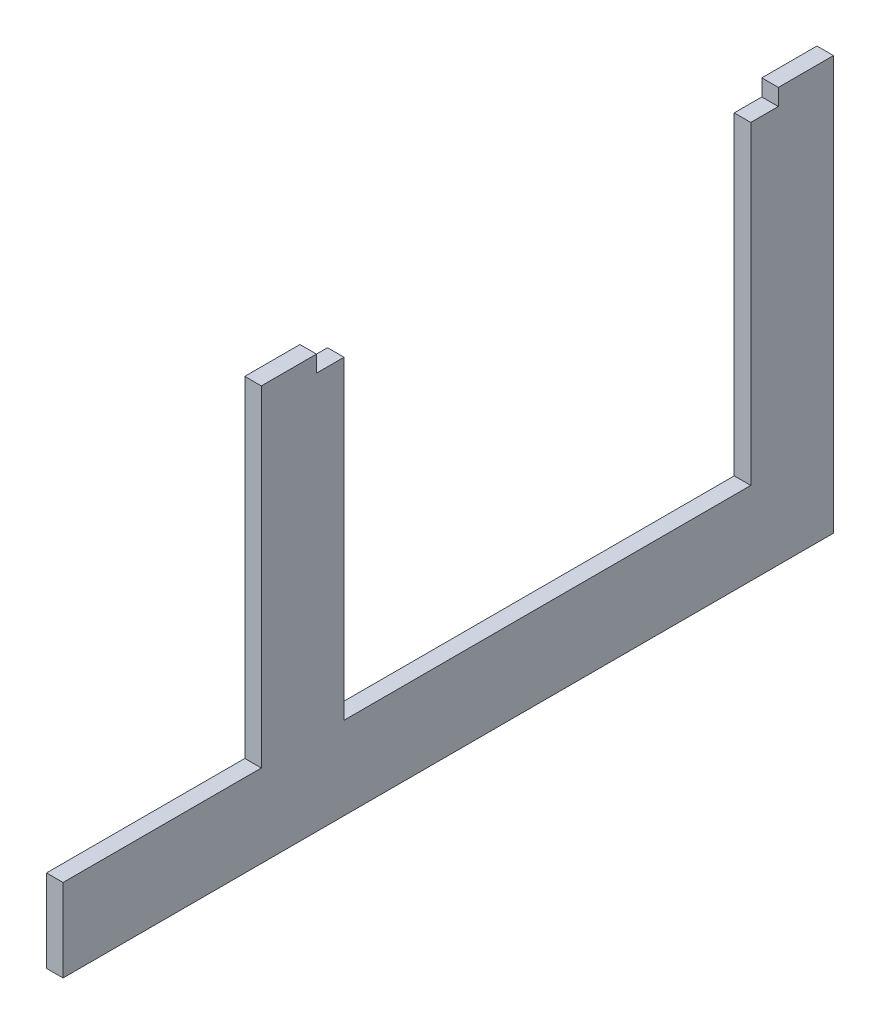
SolidWorks part; units mm, degrees
ref_plane "Front Plane" through (0, 0, 0) normal (0, 0, 1) x (1, 0, 0)
ref_plane "Top Plane" through (0, 0, 0) normal (0, 1, 0) x (1, 0, 0)
ref_plane "Right Plane" through (0, 0, 0) normal (1, 0, 0) x (0, 0, -1)
sketch "Sketch1" plane through (0, 0, 0) normal (0, 1, 0) x (1, 0, 0)
  line L0 (0, 0) -> (0, 103.7444) construction
  line L1 (-36.8722, 0) -> (36.8722, 0) construction
  line L2 (-36.8722, 0) -> (-36.8722, 103.7444)
  line L3 (-36.8722, 103.7444) -> (36.8722, 103.7444)
  line L4 (36.8722, 0) -> (36.8722, 103.7444)
  line L5 (36.8722, 103.7444) -> (36.8722, 0) construction
  line L6 (45.8722, 103.7444) -> (-45.8722, 103.7444) construction
  line L7 (21.0585, 67.686) -> (21.0585, 0)
  line L8 (-21.0585, 67.686) -> (-21.0585, 0)
  line L9 (-36.8722, 0) -> (-21.0585, 0)
  line L10 (21.0585, 0) -> (36.8722, 0)
  line L11 (31.8722, 103.7444) -> (31.8722, 88.7444) construction
  line L12 (34.8722, 103.7444) -> (34.8722, 88.7444) construction
  line L13 (31.8722, 93.7444) -> (34.8722, 93.7444) construction
  line L14 (31.8722, 10) -> (34.8722, 10) construction
  line L15 (31.8722, 88.7444) -> (34.8722, 88.7444) construction
  line L16 (31.8722, 15) -> (34.8722, 15) construction
  line L17 (31.8722, 15) -> (31.8722, 0) construction
  line L18 (34.8722, 15) -> (34.8722, 0) construction
  line L19 (33.3722, 93.7444) -> (33.3722, 88.7444) construction
  line L20 (33.3722, 15) -> (33.3722, 10) construction
  line L21 (34.8722, 100.7444) -> (-34.8722, 100.7444) construction
  line L22 (-34.8722, 100.7444) -> (-34.8722, 103.7444) construction
  line L23 (56.7, -65.95) -> (59.7, -65.95) construction
  arc A0 (21.0585, 67.686) -> (-21.0585, 67.686) centre (0, 67.686) ccw construction
  arc A1 (21.0585, 67.686) -> (-21.0585, 67.686) centre (0, 67.686) ccw
  circle A2 centre (26.5585, 78.4307) radius 1.6 construction
  circle A3 centre (-26.5585, 78.4307) radius 1.6 construction
  circle A4 centre (26.5585, 25.3138) radius 1.6 construction
  circle A5 centre (-26.5585, 25.3138) radius 1.6 construction
  circle A6 centre (26.5585, 78.4307) radius 1.6
  circle A7 centre (-26.5585, 78.4307) radius 1.6
  circle A8 centre (26.5585, 25.3138) radius 1.6
  circle A9 centre (-26.5585, 25.3138) radius 1.6
  dimension "D2" = 2
  dimension "D3" = 10
  dimension "D4" = 5
ref_plane "Plane1" through (34.8722, 0, 0) normal (1, 0, 0) x (0, 0, -1)
sketch "Sketch2" plane through (34.8722, 0, 0) normal (1, 0, 0) x (0, 0, -1)
  line L0 (103.7444, 3) -> (103.7444, -72)
  line L1 (103.7444, -72) -> (-35.95, -72)
  line L2 (0, -57) -> (0, 3)
  line L3 (0, 3) -> (10, 3)
  line L4 (10, 3) -> (10, 0)
  line L5 (10, 0) -> (15, 0)
  line L6 (15, 0) -> (15, -57)
  line L7 (15, -57) -> (88.7444, -57)
  line L8 (88.7444, -57) -> (88.7444, 0)
  line L9 (88.7444, 0) -> (93.7444, 0)
  line L10 (93.7444, 0) -> (93.7444, 3)
  line L11 (93.7444, 3) -> (103.7444, 3)
  line L12 (103.7444, 0) -> (88.7444, 0) construction
  line L13 (93.7444, 0) -> (103.7444, 0) construction
  line L14 (98.7444, 0) -> (98.7444, 3) construction
  line L15 (-35.95, -72) -> (-65.95, -72) construction
  line L16 (15, 0) -> (0, 0) construction
  line L17 (100.7444, 0) -> (103.7444, 0) construction
  line L18 (103.7444, -46) -> (0, -46) construction
  line L19 (-65.95, -72) -> (-65.95, -57) construction
  line L20 (-65.95, -45.5) -> (-65.95, 64.8444) construction
  line L21 (-35.95, -72) -> (-35.95, -57)
  line L22 (-35.95, -57) -> (-65.95, -57) construction
  line L23 (0, -57) -> (-35.95, -57)
  dimension "D1" = 46
  dimension "D2" = 72
  dimension "D3" = 15
  dimension "D4" = 30
extrude "Boss-Extrude1" add sketch "Sketch2" against normal up to vertex (3 mm away) up to point (31.8722, 0, -103.7444)
